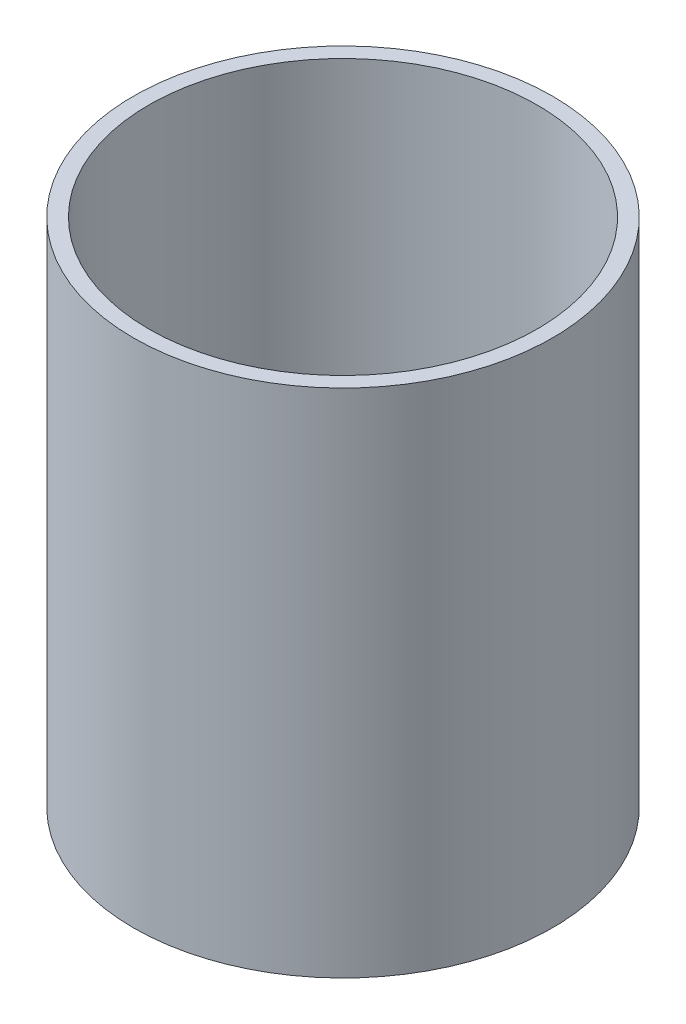
SolidWorks part; units mm, degrees
ref_plane "Front Plane" through (0, 0, 0) normal (0, 0, 1) x (1, 0, 0)
ref_plane "Top Plane" through (0, 0, 0) normal (0, 1, 0) x (1, 0, 0)
ref_plane "Right Plane" through (0, 0, 0) normal (1, 0, 0) x (0, 0, -1)
sketch "Sketch1" plane through (0, 0, 0) normal (0, 1, 0) x (1, 0, 0)
  circle A0 centre (0, 0) radius 19
  circle A1 centre (0, 0) radius 20.5
  dimension "D1" = 38
  dimension "D2" = 41
extrude "Boss-Extrude1" add sketch "Sketch1" along normal blind 50
